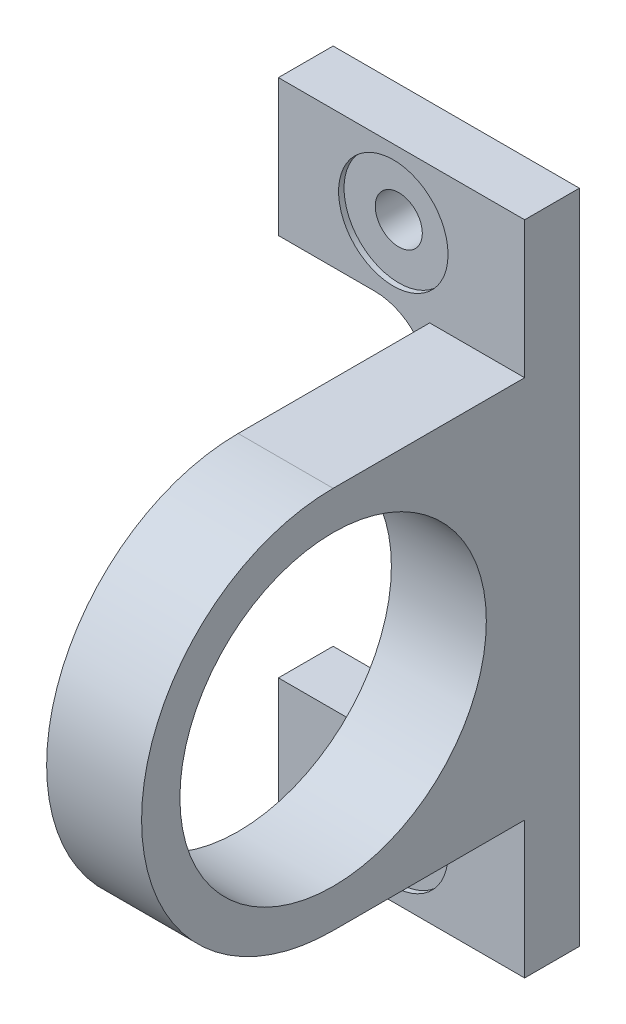
SolidWorks part; units mm, degrees
ref_plane "前视基准面" through (0, 0, 0) normal (0, 0, 1) x (1, 0, 0)
ref_plane "上视基准面" through (0, 0, 0) normal (0, 1, 0) x (1, 0, 0)
ref_plane "右视基准面" through (0, 0, 0) normal (1, 0, 0) x (0, 0, -1)
sketch "草图2" plane through (0, 0, 0) normal (0, 0, 1) x (1, 0, 0)
  line L0 (-14.7736, 24.3382) -> (-14.7736, -35.6618)
  line L1 (-14.7736, -35.6618) -> (30.2264, -35.6618)
  line L2 (7.7264, -35.6618) -> (7.7264, -23.1618)
  line L3 (21.55, -23.1618) -> (-6.0971, -23.1618)
  line L4 (-6.0971, -23.1618) -> (-6.0971, 11.8382)
  line L5 (-6.0971, 11.8382) -> (21.55, 11.8382)
  line L6 (7.7264, 11.8382) -> (7.7264, 24.3382)
  line L7 (30.2264, 24.3382) -> (-14.7736, 24.3382)
  line L8 (7.7264, 28.8603) -> (7.7264, -39.8897) construction
  line L9 (21.55, -23.1618) -> (21.55, 11.8382)
  line L10 (30.2264, 24.3382) -> (30.2264, -35.6618)
  line L11 (-18.1559, -5.6618) -> (33.2411, -5.6618) construction
  line L12 (44.0218, -5.6618) -> (44.0218, 26.2521) construction
  point P16 (-6.0971, -5.6618)
  point P17 (-14.7736, -5.6618)
  dimension "D1" = 45
  dimension "D2" = 35
  dimension "D3" = 60
extrude "凸台-拉伸2" add sketch "草图2" along normal blind 5 contours L6 L7 L0 L1 L2 L3 L4 L5 | L10 L7 L6 L5 L9 L3 L2 L1 region at (-3.5236, 23.6974, 0) region at (18.9764, 23.6974, 0)
sketch "草图4" plane through (0, 0, 5) normal (0, 0, 1) x (1, 0, 0)
  line L0 (-18.165, -5.6618) -> (33.9165, -5.6618) construction
  line L1 (-14.7736, 24.3382) -> (-14.7736, -35.6618) construction
  line L2 (-14.7736, -23.1618) -> (-6.0971, -23.1618)
  line L3 (-14.7736, -23.1618) -> (-14.7736, 11.8382)
  line L4 (-14.7736, 11.8382) -> (-6.0971, 11.8382)
  line L5 (-6.0971, -23.1618) -> (-6.0971, 11.8382)
  line L6 (-6.0971, -23.1618) -> (-6.0971, 11.8382) construction
  line L7 (7.7264, -39.813) -> (7.7264, 28.1228) construction
  line L8 (30.2264, 11.8382) -> (21.55, 11.8382)
  line L9 (21.55, -23.1618) -> (21.55, 11.8382)
  line L10 (30.2264, -23.1618) -> (21.55, -23.1618)
  line L11 (30.2264, -23.1618) -> (30.2264, 11.8382)
  point P17 (-14.7736, -5.6618)
  dimension "D1" = 35
extrude "凸台-拉伸15" add sketch "草图4" along normal blind 35
sketch "草图5" plane through (-14.7736, 0, 0) normal (-1, 0, 0) x (0, 0, 1)
  line L0 (0, -5.6618) -> (40, -5.6618)
  line L1 (0, 24.3382) -> (0, -35.6618) construction
  line L2 (40, 11.8382) -> (40, -23.1618) construction
  line L3 (22.5, 11.8382) -> (40, 11.8382)
  line L4 (40, 11.8382) -> (40, -23.1618)
  line L5 (40, -23.1618) -> (22.5, -23.1618)
  circle A0 centre (22.5, -5.6618) radius 17.5
  line M5 (5, -23.1618) -> (40, -23.1618)
  line M6 (40, -23.1618) -> (40, 11.8382)
  line M7 (40, 11.8382) -> (5, 11.8382)
  dimension "D1" = 35
extrude "切除-拉伸1" cut sketch "草图5" against normal blind 45 contours A0 M5 M6 | A0 M6 M7 region at (-14.7736, 7.9293, 36.0911) region at (-14.7736, -19.2528, 36.0911)
sketch "草图6" plane through (-14.7736, 0, 0) normal (-1, 0, 0) x (0, 0, 1)
  circle A0 centre (22.5, -5.6618) radius 14
  dimension "D1" = 28
extrude "切除-拉伸2" cut sketch "草图6" against normal blind 45
fillet "圆角1" radius 5 4 edges at (-6.0971, 11.8382, 2.5) (21.55, 11.8382, 2.5) (-6.0971, -23.1618, 2.5) (21.55, -23.1618, 2.5)
sketch "草图7" plane through (-6.0971, 0, 0) normal (1, 0, 0) x (0, 0, -1)
  circle A0 centre (-22.5, -5.6618) radius 15
  circle A1 centre (-22.5, -5.6618) radius 13
extrude "凸台-拉伸16" add sketch "草图7" against normal blind 1
sketch "草图8" plane through (21.55, 0, 0) normal (-1, 0, 0) x (0, 0, 1)
  circle A0 centre (22.5, -5.6618) radius 15
  circle A1 centre (22.5, -5.6618) radius 10
sketch "草图9" plane through (0, 0, 5) normal (0, 0, 1) x (1, 0, 0)
  line L0 (7.7264, 24.3382) -> (7.7264, -35.6618)
  line L13 (30.2264, 24.3382) -> (-14.7736, 24.3382) construction
  line L14 (-14.7736, -35.6618) -> (30.2264, -35.6618) construction
sketch "草图11" plane through (0, 0, 5) normal (0, 0, 1) x (1, 0, 0)
  line L0 (-14.7736, 18.0882) -> (30.2264, 18.0882)
  line L1 (-14.7736, 24.3382) -> (-14.7736, 11.8382) construction
  line L2 (30.2264, 24.3382) -> (30.2264, 11.8382) construction
  line L3 (7.7264, 24.3382) -> (7.7264, -35.6618) construction
  line L4 (30.2264, 24.3382) -> (-14.7736, 24.3382) construction
  line L5 (-14.7736, -35.6618) -> (30.2264, -35.6618) construction
  line L6 (7.7264, -5.6618) -> (45.6912, -5.6618) construction
  line L10 (-14.7736, -29.4118) -> (30.2264, -29.4118)
  line L11 (-14.7736, -23.1618) -> (-14.7736, -35.6618) construction
  point P4 (-2.7736, 18.0882)
  point P16 (-2.7736, -29.4118)
  point P18 (18.2264, -29.4118)
  point P25 (18.2264, 18.0882)
  dimension "D1" = 12
split "分割1" trim tools "草图9" bodies to split 111 resulting bodies 117 118
delete or keep bodies "实体-删除/保留 2" type delete bodies bodies 117
hole_wizard "打孔尺寸(%根据六角头螺)栓 全螺纹的类型1" positions "3D草图2" profile "草图13" counterbore size "M4" standard "GB"
sketch3d "3D草图2"
  point P0 (18.2264, 18.0882, 5)
  point P3 (18.2264, -29.4118, 5)
sketch "草图13" plane through (18.2264, 18.0882, 5) normal (1, 0, 0) x (0, -1, 0)
  line L0 (0, 0) -> (0, 6.2919)
  line L1 (0, 6.2919) -> (2.15, 5)
  line L2 (2.15, 5) -> (2.15, 0.5)
  line L3 (2.15, 0.5) -> (5, 0.5)
  line L4 (5, 0.5) -> (5, 0)
  line L5 (5, 0) -> (0, 0)
  line L10 (0, 6.2919) -> (-2.15, 5) construction
  line L11 (0, -6.35) -> (0, 107.95) construction
  dimension "孔直径" = 4.3
  dimension "孔深度" = 5
  dimension "柱形沉头孔直径" = 10
  dimension "柱形沉头孔深度" = 0.5
  dimension "导头角度" = 118
